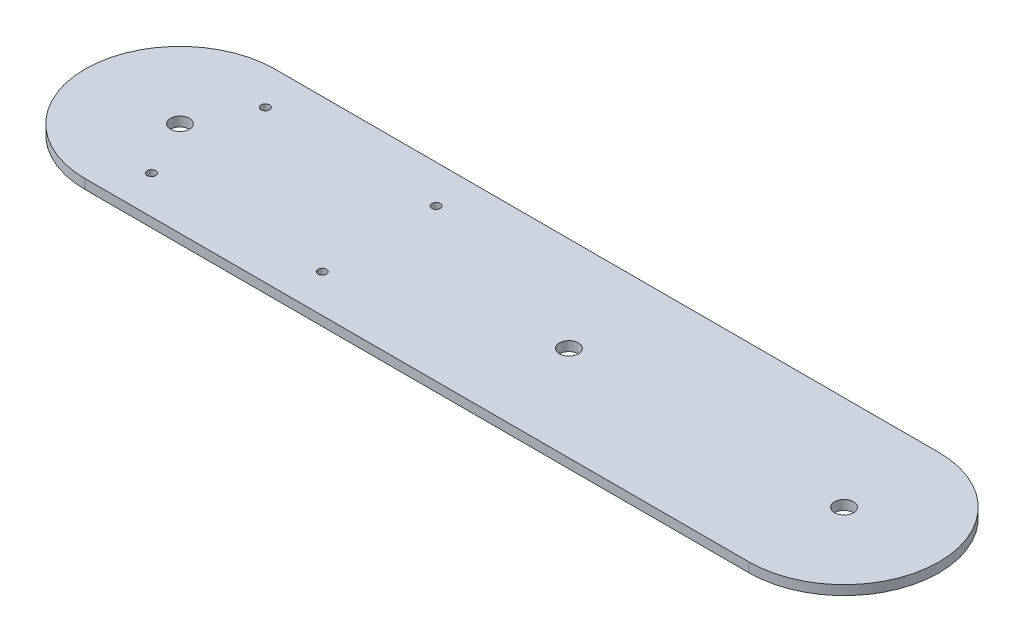
SolidWorks part; units mm, degrees
ref_plane "Front Plane" through (0, 0, 0) normal (0, 0, 1) x (1, 0, 0)
ref_plane "Top Plane" through (0, 0, 0) normal (0, 1, 0) x (1, 0, 0)
ref_plane "Right Plane" through (0, 0, 0) normal (1, 0, 0) x (0, 0, -1)
sketch "Sketch1" plane through (0, 0, 0) normal (0, 1, 0) x (1, 0, 0)
  line L0 (0, 0) -> (350, 0) construction
  line L1 (0, 50) -> (350, 50)
  line L2 (0, -50) -> (350, -50)
  circle A0 centre (0, 0) radius 5
  arc A1 (0, 50) -> (0, -50) centre (0, 0) ccw
  arc A2 (350, -50) -> (350, 50) centre (350, 0) ccw
  circle A3 centre (350, 0) radius 5
  dimension "D1" = 10
  dimension "D2" = 100
  dimension "D4" = 100
  dimension "D5" = 10
  dimension "D3" = 350
extrude "Boss-Extrude1" add sketch "Sketch1" along normal blind 5
sketch "Sketch2" plane through (0, 5, 0) normal (0, 1, 0) x (1, 0, 0)
  line L0 (15, 0) -> (0, 0) construction
  line L1 (15, 30) -> (105, 30) construction
  line L2 (15, 30) -> (15, -30) construction
  line L3 (15, -30) -> (105, -30) construction
  line L4 (105, 30) -> (105, -30) construction
  line L5 (15, 30) -> (105, -30) construction
  line L11 (25, -35) -> (95, 35) construction
  line L12 (25, 35) -> (95, -35) construction
  circle A2 centre (15, -30) radius 2.25
  circle A3 centre (105, -30) radius 2.25
  circle A4 centre (105, 30) radius 2.25
  circle A5 centre (15, 30) radius 2.25
  circle A7 centre (205, 0) radius 5 construction
  circle A8 centre (205, 0) radius 5
  point P1 (60, 0)
  dimension "D4" = 2
  dimension "D6" = 70
  dimension "D1" = 60
  dimension "D2" = 90
  dimension "D3" = 15
  dimension "D7" = 70
  dimension "D5" = 2
extrude "Cut-Extrude1" cut sketch "Sketch2" against normal blind 5
sketch "Sketch3" [suppressed] plane through (0, 5, 0) normal (0, 1, 0) x (1, 0, 0)
  line L0 (15, 30) -> (105, -30) construction
  line L2 (25, -35) -> (95, -35)
  line L3 (25, -35) -> (25, 35)
  line L4 (25, 35) -> (95, 35)
  line L5 (95, -35) -> (95, 35)
  line L6 (25, -35) -> (95, 35) construction
  line L7 (25, 35) -> (95, -35) construction
  point P4 (60, 0)
  dimension "D1" = 70
  dimension "D2" = 70
extrude "Cut-Extrude2" [suppressed] cut sketch "Sketch3" against normal blind 20
